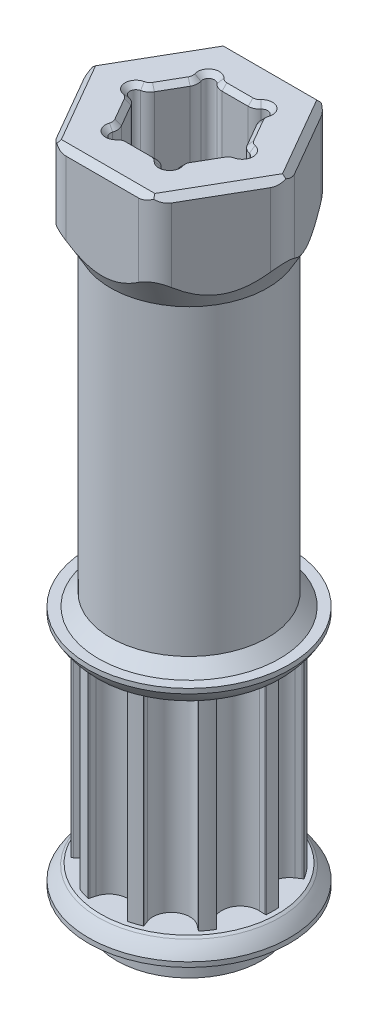
SolidWorks part; units mm, degrees
other "DetailItem2"
material "Markforged"
ref_plane "Front Plane" through (0, 0, 0) normal (0, 0, 1) x (1, 0, 0)
ref_plane "Top Plane" through (0, 0, 0) normal (0, 1, 0) x (1, 0, 0)
ref_plane "Right Plane" through (0, 0, 0) normal (1, 0, 0) x (0, 0, -1)
ref_axis "Centerline" through (0, 8.7312, 0) along (0, -1, 0)
sketch "Sketch1" plane through (0, 0, 0) normal (0, 1, 0) x (1, 0, 0)
  circle A0 centre (0, 0) radius 4.3936
  dimension "OuterDiameter" = 8.7873
extrude "ToothOD" add sketch "Sketch1" along normal mid plane 10.668
sketch "Sketch2" plane through (0, 0, 0) normal (0, 1, 0) x (1, 0, 0)
  line L0 (0, 3.2252) -> (50000, 3.2252) construction
  line L1 (0, 4.3936) -> (50000, 4.3936) construction
  line L2 (0, 0) -> (0, 50000) construction
  arc A0 (-0.937, 3.9437) -> (0, 3.2252) centre (0, 4.1955) ccw
  arc A1 (-1.0404, 4.2687) -> (1.0404, 4.2687) centre (0, 0) cw
  circle A2 centre (0, 0) radius 4.3936 construction
  arc A3 (-0.937, 3.9437) -> (-1.0078, 4.1955) centre (-11.9754, 0.9773) ccw
  arc A4 (-1.0078, 4.1955) -> (-1.0404, 4.2687) centre (-1.2954, 4.1111) ccw
  circle A5 centre (0, 0) radius 4.3936 construction
  arc A6 (0.937, 3.9437) -> (1.0078, 4.1955) centre (11.9754, 0.9773) cw
  arc A7 (1.0078, 4.1955) -> (1.0404, 4.2687) centre (1.2954, 4.1111) cw
  arc A8 (0, 3.2252) -> (0.937, 3.9437) centre (0, 4.1955) ccw
  dimension "D1" = 1.9406
  dimension "D3" = 22.86
  dimension "D4" = 0.5994
  dimension "D2" = 1.1684
  dimension "D5" = 1.2954
extrude "ToothProfile" cut sketch "Sketch2" against normal through all both and the other way through all
pattern_circular "ToothPattern" count 10 over 360 about axis through (0, 5.334, 0) along (0, -1, 0) of "ToothProfile"
sketch "Sketch4" plane through (0, 0, 0) normal (0, 0, 1) x (1, 0, 0)
  line L0 (0, -5.334) -> (4.6476, -5.334)
  line L1 (0, -6.35) -> (5.2826, -6.35)
  line L2 (0, -6.35) -> (0, -5.334)
  line L3 (5.2826, -6.35) -> (5.2826, -6.096)
  line L4 (0, 0) -> (50000, 0) construction
  line L5 (5.2826, 6.35) -> (5.2826, 6.096)
  line L6 (0, 6.35) -> (0, 5.334)
  line L7 (0, 6.35) -> (5.2826, 6.35)
  line L8 (0, 5.334) -> (4.6476, 5.334)
  arc A0 (4.6476, -5.334) -> (4.7746, -5.4266) centre (3.2071, -7.4422) cw
  arc A2 (4.7746, -5.4266) -> (5.2826, -6.096) centre (2.4988, -7.6813) cw
  arc A3 (4.7746, 5.4266) -> (5.2826, 6.096) centre (2.4988, 7.6813) ccw
  arc A4 (4.6476, 5.334) -> (4.7746, 5.4266) centre (3.2071, 7.4422) ccw
  dimension "D5" = 2.5534
  dimension "D6" = 3.2036
  dimension "FlangeID" = 4.6476
  dimension "FlangeOD" = 5.2826
  dimension "D1" = 1.016
  dimension "D2" = 0.254
  dimension "D3" = 5.334
  dimension "D4" = 12.7
  dimension "D7" = 0.762
  dimension "D8" = 0.6694
  dimension "D10" = 0.508
revolve "Flange" add sketch "Sketch4" angle 360 about axis through (0, 8.7312, 0) along (0, -1, 0)
sketch "Sketch7" plane through (0, 0, 0) normal (0, -1, 0) x (1, 0, 0)
  line L1 (1.3968, 2.4193) -> (-1.3968, 2.4193)
  line L2 (-1.3968, 2.4193) -> (-2.7936, 0)
  line L3 (-2.7936, 0) -> (-1.3968, -2.4193)
  line L4 (-1.3968, -2.4193) -> (1.3968, -2.4193)
  line L5 (1.3968, -2.4193) -> (2.7936, 0)
  line L6 (2.7936, 0) -> (1.3968, 2.4193)
  circle A0 centre (0, 0) radius 2.4193 construction
  dimension "HexBoreDi," = 4.8387
extrude "Bore" cut sketch "Sketch7" against normal through all both and the other way through all
sketch "Sketch9" plane through (0, 6.35, 0) normal (0, 1, 0) x (1, 0, 0)
  arc A0 (-3.6864, -3.6864) -> (3.6864, -3.6864) centre (0, 0) cw construction
  text T0 "10" font "Arial Rounded MT Bold" height 4.572
  point P3 (0, 5.2133)
  dimension "D1" = 5.2133
  dimension "D2" = 270
extrude "Large Tooth Count" [suppressed] cut sketch "Sketch9" against normal blind 0.4 and the other way through all
sketch "Sketch10" plane through (0, -6.35, 0) normal (0, -1, 0) x (1, 0, 0)
  line L6 (1.3968, 2.4193) -> (-1.3968, 2.4193)
  line L7 (2.7936, 0) -> (1.3968, 2.4193)
  line L8 (1.3968, -2.4193) -> (2.7936, 0)
  line L9 (-1.3968, -2.4193) -> (1.3968, -2.4193)
  line L10 (-2.7936, 0) -> (-1.3968, -2.4193)
  line L11 (-1.3968, 2.4193) -> (-2.7936, 0)
  line L12 (1.3968, 2.4193) -> (-1.3968, 2.4193)
  line L13 (2.7936, 0) -> (1.3968, 2.4193)
  line L14 (1.3968, -2.4193) -> (2.7936, 0)
  line L15 (-1.3968, -2.4193) -> (1.3968, -2.4193)
  line L16 (-2.7936, 0) -> (-1.3968, -2.4193)
  line L17 (-1.3968, 2.4193) -> (-2.7936, 0)
  circle A0 centre (0, 0) radius 3.81
  dimension "D2" = 7.62
  dimension "D1" = 0
extrude "Boss-Extrude1" add sketch "Sketch10" along normal blind 1.524
sketch "Sketch11" plane through (0, 6.35, 0) normal (0, 1, 0) x (1, 0, 0)
  line L6 (2.7936, 0) -> (1.3968, 2.4193)
  line L7 (1.3968, -2.4193) -> (2.7936, 0)
  line L8 (-1.3968, -2.4193) -> (1.3968, -2.4193)
  line L9 (-2.7936, 0) -> (-1.3968, -2.4193)
  line L10 (-1.3968, 2.4193) -> (-2.7936, 0)
  line L11 (1.3968, 2.4193) -> (-1.3968, 2.4193)
  line L12 (2.7936, 0) -> (1.3968, 2.4193)
  line L13 (1.3968, -2.4193) -> (2.7936, 0)
  line L14 (-1.3968, -2.4193) -> (1.3968, -2.4193)
  line L15 (-2.7936, 0) -> (-1.3968, -2.4193)
  line L16 (-1.3968, 2.4193) -> (-2.7936, 0)
  line L17 (1.3968, 2.4193) -> (-1.3968, 2.4193)
  circle A0 centre (0, 0) radius 4.1275
  dimension "D2" = 8.255
  dimension "D1" = 0
extrude "Boss-Extrude2" add sketch "Sketch11" along normal blind 18.9738
sketch "Sketch14" plane through (0, 25.3238, 0) normal (0, 1, 0) x (1, 0, 0)
  line L1 (2.6396, -4.572) -> (5.2793, 0)
  line L2 (5.2793, 0) -> (2.6396, 4.572)
  line L3 (2.6396, 4.572) -> (-2.6396, 4.572)
  line L4 (-2.6396, 4.572) -> (-5.2793, 0)
  line L5 (-5.2793, 0) -> (-2.6396, -4.572)
  line L6 (-1.3968, 2.4193) -> (-2.7936, 0)
  line L7 (1.3968, 2.4193) -> (-1.3968, 2.4193)
  line L8 (2.7936, 0) -> (1.3968, 2.4193)
  line L9 (1.3968, -2.4193) -> (2.7936, 0)
  line L10 (-1.3968, -2.4193) -> (1.3968, -2.4193)
  line L11 (-2.7936, 0) -> (-1.3968, -2.4193)
  line L12 (-1.3968, 2.4193) -> (-2.7936, 0)
  line L13 (1.3968, 2.4193) -> (-1.3968, 2.4193)
  line L14 (2.7936, 0) -> (1.3968, 2.4193)
  line L15 (1.3968, -2.4193) -> (2.7936, 0)
  line L16 (-1.3968, -2.4193) -> (1.3968, -2.4193)
  line L17 (-2.7936, 0) -> (-1.3968, -2.4193)
  line L18 (-2.6396, -4.572) -> (2.6396, -4.572)
  circle A0 centre (0, 0) radius 4.572 construction
  dimension "D2" = 9.144
  dimension "D1" = 0
extrude "Boss-Extrude3" add sketch "Sketch14" along normal blind 3.175
sketch "Sketch12" plane through (0, -7.874, 0) normal (0, -1, 0) x (1, 0, 0)
  circle A0 centre (-1.3968, 2.4193) radius 0.3175
  circle A1 centre (1.3968, 2.4193) radius 0.3175
  circle A2 centre (2.7936, 0) radius 0.3175
  circle A3 centre (1.3968, -2.4193) radius 0.3175
  circle A4 centre (-1.3968, -2.4193) radius 0.3175
  circle A5 centre (-2.7936, 0) radius 0.3175
  dimension "D1" = 0.635
extrude "Cut-Extrude1" cut sketch "Sketch12" against normal through all
fillet "Fillet1" radius 0.635 12 edges at (1.5556, 10.3124, -2.1444) (1.0793, 10.3124, -2.4193) (-1.0793, 10.3124, -2.4193) (-1.5556, 10.3124, -2.1444) (-2.6349, 10.3124, -0.275) (-2.6349, 10.3124, 0.275) (-1.5556, 10.3124, 2.1444) (-1.0793, 10.3124, 2.4193) (1.0793, 10.3124, 2.4193) (1.5556, 10.3124, 2.1444) (2.6349, 10.3124, 0.275) (2.6349, 10.3124, -0.275)
chamfer "Chamfer2" distance 0.254 angle 45 48 edges at (0, -7.874, -2.4193) (0.9461, -7.874, -2.4747) (-0.9461, -7.874, -2.4747) (1.5556, -7.874, -2.6943) (-1.5556, -7.874, -2.6943) (1.6701, -7.874, -2.0567) (-1.6701, -7.874, -2.0567) (2.0952, -7.874, -1.2097) (-2.0952, -7.874, -1.2097) (2.6162, -7.874, -0.418) (-2.6162, -7.874, -0.418) (3.1111, -7.874, 0) (-3.1111, -7.874, 0) (2.6162, -7.874, 0.418) (-2.6162, -7.874, 0.418) (2.0952, -7.874, 1.2097) (-2.0952, -7.874, 1.2097) (1.6701, -7.874, 2.0567) (-1.6701, -7.874, 2.0567) (1.5556, -7.874, 2.6943) (-1.5556, -7.874, 2.6943) (0.9461, -7.874, 2.4747) (-0.9461, -7.874, 2.4747) (0, -7.874, 2.4193) (0, 28.4988, 2.4193) (0.9461, 28.4988, 2.4747) (-0.9461, 28.4988, 2.4747) (1.5556, 28.4988, 2.6943) (-1.5556, 28.4988, 2.6943) (1.6701, 28.4988, 2.0567) (-1.6701, 28.4988, 2.0567) (2.0952, 28.4988, 1.2097) (-2.0952, 28.4988, 1.2097) (2.6162, 28.4988, 0.418) (-2.6162, 28.4988, 0.418) (3.1111, 28.4988, 0) (-3.1111, 28.4988, 0) (2.6162, 28.4988, -0.418) (-2.6162, 28.4988, -0.418) (2.0952, 28.4988, -1.2097) (-2.0952, 28.4988, -1.2097) (1.6701, 28.4988, -2.0567) (-1.6701, 28.4988, -2.0567) (1.5556, 28.4988, -2.6943) (-1.5556, 28.4988, -2.6943) (0.9461, 28.4988, -2.4747) (-0.9461, 28.4988, -2.4747) (0, 28.4988, -2.4193)
chamfer "Chamfer1" distance 0.635 angle 45 2 edges at (0, 6.35, 4.1275) (0, -6.35, -3.81)
chamfer "Chamfer3" distance 1.397 angle 60 1 edges at (0, 25.3238, 4.1275) first distance on face at (0, 25.3238, 4.1275)
chamfer "Chamfer4" distance 0.3175 angle 45 6 edges at (0, 28.4988, 4.572) (-3.9595, 28.4988, 2.286) (-3.9595, 28.4988, -2.286) (0, 28.4988, -4.572) (3.9595, 28.4988, 2.286) (3.9595, 28.4988, -2.286)
fillet "Fillet2" radius 1.27 6 edges at (-2.6396, 26.5402, -4.572) (-5.2793, 26.5402, 0) (-2.6396, 26.5402, 4.572) (2.6396, 26.5402, 4.572) (5.2793, 26.5402, 0) (2.6396, 26.5402, -4.572)
equation "\"OuterDiameter@Sketch1\"= \"OD\""
equation "\"Teeth\"= \"No_Teeth\""
equation "\"PD\"= \"No_Teeth\" * 3mm / pi"
equation "\"OD\"= \"PD\" - .030"
equation "\"ToothCount@ToothPattern\" = \"Teeth\""
equation "\"Angle\"= 360 / \"Teeth\""
equation "\"AngleSpacing@ToothPattern\" = \"Angle\""
equation "\"FlangeID@Sketch4\"=\"OD\"/2+.01"
equation "\"FlangeOD@Sketch4\"=\"PD\"/2+.02"
equation "\"D3@Sketch4\"=\"Tooth_Face_Length\"/2"
equation "\"Bearing_Feature\"= \"Bearing_Boss\""
equation "\"TopBearingBoss\" = IIF ( \"Bearing_Feature\" > 0 , \"unsuppressed\" , \"suppressed\" )"
equation "\"HexBore\"= \"Hex_Bore\" + \"Print_Tolerance\""
equation "\"HexBoreDi,@Sketch7\"= \"HexBore\""
equation "\"Large Tooth Count\" = iif ( \"No_Teeth\" < \"TextTooth\" , \"suppressed\" , \"unsuppressed\" )"
equation "\"Small Tooth Count\"= iif ( \"No_Teeth\" < \"TextTooth\" , \"unsuppressed\" , \"suppressed\" )"
equation "\"BottomBearingBoss\" = iif ( \"Bearing_Feature\" > 1 , \"unsuppressed\" , \"suppressed\" )"
equation "\"ToothFaceLength@ToothOD\" = \"Tooth_Face_Length\""
equation "\"D4@Sketch4\"=\"Width_No_Flange\""
equation "\"D1@Sketch9\"=\"HexBore\"/2+.11"
equation "\"TextTooth\"= iif ( \"Hex_Bore\" <= .380 , 23 , iif ( \"Hex_Bore\" <= .505 , 25 , 16 ) )"
